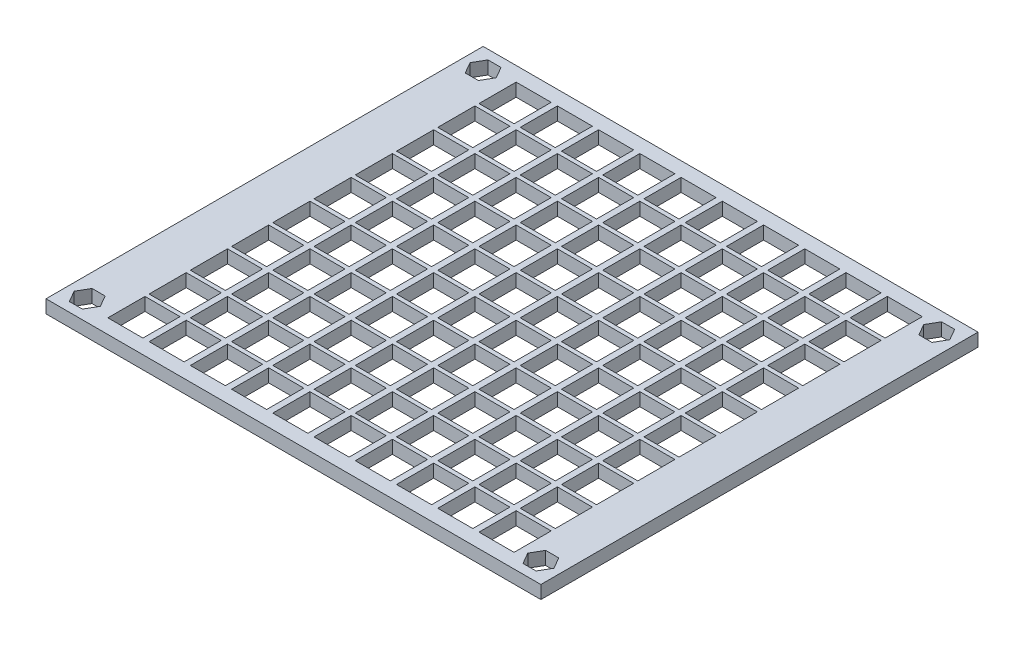
SolidWorks part; units mm, degrees
ref_plane "Front Plane" through (0, 0, 0) normal (0, 0, 1) x (1, 0, 0)
ref_plane "Top Plane" through (0, 0, 0) normal (0, 1, 0) x (1, 0, 0)
ref_plane "Right Plane" through (0, 0, 0) normal (1, 0, 0) x (0, 0, -1)
sketch "Sketch1" plane through (0, 0, 0) normal (0, 1, 0) x (1, 0, 0)
  line L0 (115, 101) -> (5, 101) construction
  line L1 (0, 0) -> (120, 0)
  line L2 (0, 0) -> (0, 106)
  line L3 (0, 106) -> (120, 106)
  line L4 (120, 0) -> (120, 106)
  line L6 (115, 101) -> (115, 5) construction
  line L8 (6.5877, 98.25) -> (8.1754, 101)
  line L9 (8.1754, 101) -> (6.5877, 103.75)
  line L10 (6.5877, 103.75) -> (3.4123, 103.75)
  line L11 (3.4123, 103.75) -> (1.8246, 101)
  line L12 (1.8246, 101) -> (3.4123, 98.25)
  line L13 (3.4123, 98.25) -> (6.5877, 98.25)
  line L14 (21.5, 12.5) -> (21.5, 3.5)
  line L15 (11.5, 12.5) -> (20, 12.5)
  line L16 (11.5, 12.5) -> (11.5, 3.5)
  line L17 (11.5, 3.5) -> (20, 3.5)
  line L18 (20, 12.5) -> (20, 3.5)
  line L19 (21.5, 12.5) -> (30, 12.5)
  line L20 (30, 12.5) -> (30, 3.5)
  line L21 (21.5, 3.5) -> (30, 3.5)
  line L22 (31.5, 12.5) -> (31.5, 3.5)
  line L23 (31.5, 12.5) -> (40, 12.5)
  line L24 (40, 12.5) -> (40, 3.5)
  line L25 (31.5, 3.5) -> (40, 3.5)
  line L26 (41.5, 12.5) -> (41.5, 3.5)
  line L27 (41.5, 12.5) -> (50, 12.5)
  line L28 (50, 12.5) -> (50, 3.5)
  line L29 (41.5, 3.5) -> (50, 3.5)
  line L30 (51.5, 12.5) -> (51.5, 3.5)
  line L31 (51.5, 12.5) -> (60, 12.5)
  line L32 (60, 12.5) -> (60, 3.5)
  line L33 (51.5, 3.5) -> (60, 3.5)
  line L34 (61.5, 12.5) -> (61.5, 3.5)
  line L35 (61.5, 12.5) -> (70, 12.5)
  line L36 (70, 12.5) -> (70, 3.5)
  line L37 (61.5, 3.5) -> (70, 3.5)
  line L38 (71.5, 12.5) -> (71.5, 3.5)
  line L39 (71.5, 12.5) -> (80, 12.5)
  line L40 (80, 12.5) -> (80, 3.5)
  line L41 (71.5, 3.5) -> (80, 3.5)
  line L42 (81.5, 12.5) -> (81.5, 3.5)
  line L43 (81.5, 12.5) -> (90, 12.5)
  line L44 (90, 12.5) -> (90, 3.5)
  line L45 (81.5, 3.5) -> (90, 3.5)
  line L46 (91.5, 12.5) -> (91.5, 3.5)
  line L47 (91.5, 12.5) -> (100, 12.5)
  line L48 (100, 12.5) -> (100, 3.5)
  line L49 (91.5, 3.5) -> (100, 3.5)
  line L50 (101.5, 12.5) -> (101.5, 3.5)
  line L51 (101.5, 12.5) -> (110, 12.5)
  line L52 (110, 12.5) -> (110, 3.5)
  line L53 (101.5, 3.5) -> (110, 3.5)
  line L54 (21.5, 22.5) -> (21.5, 13.5)
  line L55 (21.5, 22.5) -> (30, 22.5)
  line L56 (30, 22.5) -> (30, 13.5)
  line L57 (21.5, 13.5) -> (30, 13.5)
  line L58 (31.5, 22.5) -> (31.5, 13.5)
  line L59 (31.5, 22.5) -> (40, 22.5)
  line L60 (40, 22.5) -> (40, 13.5)
  line L61 (31.5, 13.5) -> (40, 13.5)
  line L62 (41.5, 22.5) -> (41.5, 13.5)
  line L63 (41.5, 22.5) -> (50, 22.5)
  line L64 (50, 22.5) -> (50, 13.5)
  line L65 (41.5, 13.5) -> (50, 13.5)
  line L66 (51.5, 22.5) -> (51.5, 13.5)
  line L67 (51.5, 22.5) -> (60, 22.5)
  line L68 (60, 22.5) -> (60, 13.5)
  line L69 (51.5, 13.5) -> (60, 13.5)
  line L70 (61.5, 22.5) -> (61.5, 13.5)
  line L71 (61.5, 22.5) -> (70, 22.5)
  line L72 (70, 22.5) -> (70, 13.5)
  line L73 (61.5, 13.5) -> (70, 13.5)
  line L74 (71.5, 22.5) -> (71.5, 13.5)
  line L75 (71.5, 22.5) -> (80, 22.5)
  line L76 (80, 22.5) -> (80, 13.5)
  line L77 (71.5, 13.5) -> (80, 13.5)
  line L78 (81.5, 22.5) -> (81.5, 13.5)
  line L79 (81.5, 22.5) -> (90, 22.5)
  line L80 (90, 22.5) -> (90, 13.5)
  line L81 (81.5, 13.5) -> (90, 13.5)
  line L82 (91.5, 22.5) -> (91.5, 13.5)
  line L83 (91.5, 22.5) -> (100, 22.5)
  line L84 (100, 22.5) -> (100, 13.5)
  line L85 (91.5, 13.5) -> (100, 13.5)
  line L86 (101.5, 22.5) -> (101.5, 13.5)
  line L87 (101.5, 22.5) -> (110, 22.5)
  line L88 (110, 22.5) -> (110, 13.5)
  line L89 (101.5, 13.5) -> (110, 13.5)
  line L90 (21.5, 32.5) -> (21.5, 23.5)
  line L91 (21.5, 32.5) -> (30, 32.5)
  line L92 (30, 32.5) -> (30, 23.5)
  line L93 (21.5, 23.5) -> (30, 23.5)
  line L94 (31.5, 32.5) -> (31.5, 23.5)
  line L95 (31.5, 32.5) -> (40, 32.5)
  line L96 (40, 32.5) -> (40, 23.5)
  line L97 (31.5, 23.5) -> (40, 23.5)
  line L98 (41.5, 32.5) -> (41.5, 23.5)
  line L99 (41.5, 32.5) -> (50, 32.5)
  line L100 (50, 32.5) -> (50, 23.5)
  line L101 (41.5, 23.5) -> (50, 23.5)
  line L102 (51.5, 32.5) -> (51.5, 23.5)
  line L103 (51.5, 32.5) -> (60, 32.5)
  line L104 (60, 32.5) -> (60, 23.5)
  line L105 (51.5, 23.5) -> (60, 23.5)
  line L106 (61.5, 32.5) -> (61.5, 23.5)
  line L107 (61.5, 32.5) -> (70, 32.5)
  line L108 (70, 32.5) -> (70, 23.5)
  line L109 (61.5, 23.5) -> (70, 23.5)
  line L110 (71.5, 32.5) -> (71.5, 23.5)
  line L111 (71.5, 32.5) -> (80, 32.5)
  line L112 (80, 32.5) -> (80, 23.5)
  line L113 (71.5, 23.5) -> (80, 23.5)
  line L114 (81.5, 32.5) -> (81.5, 23.5)
  line L115 (81.5, 32.5) -> (90, 32.5)
  line L116 (90, 32.5) -> (90, 23.5)
  line L117 (81.5, 23.5) -> (90, 23.5)
  line L118 (91.5, 32.5) -> (91.5, 23.5)
  line L119 (91.5, 32.5) -> (100, 32.5)
  line L120 (100, 32.5) -> (100, 23.5)
  line L121 (91.5, 23.5) -> (100, 23.5)
  line L122 (101.5, 32.5) -> (101.5, 23.5)
  line L123 (101.5, 32.5) -> (110, 32.5)
  line L124 (110, 32.5) -> (110, 23.5)
  line L125 (101.5, 23.5) -> (110, 23.5)
  line L126 (21.5, 42.5) -> (21.5, 33.5)
  line L127 (21.5, 42.5) -> (30, 42.5)
  line L128 (30, 42.5) -> (30, 33.5)
  line L129 (21.5, 33.5) -> (30, 33.5)
  line L130 (31.5, 42.5) -> (31.5, 33.5)
  line L131 (31.5, 42.5) -> (40, 42.5)
  line L132 (40, 42.5) -> (40, 33.5)
  line L133 (31.5, 33.5) -> (40, 33.5)
  line L134 (41.5, 42.5) -> (41.5, 33.5)
  line L135 (41.5, 42.5) -> (50, 42.5)
  line L136 (50, 42.5) -> (50, 33.5)
  line L137 (41.5, 33.5) -> (50, 33.5)
  line L138 (51.5, 42.5) -> (51.5, 33.5)
  line L139 (51.5, 42.5) -> (60, 42.5)
  line L140 (60, 42.5) -> (60, 33.5)
  line L141 (51.5, 33.5) -> (60, 33.5)
  line L142 (61.5, 42.5) -> (61.5, 33.5)
  line L143 (61.5, 42.5) -> (70, 42.5)
  line L144 (70, 42.5) -> (70, 33.5)
  line L145 (61.5, 33.5) -> (70, 33.5)
  line L146 (71.5, 42.5) -> (71.5, 33.5)
  line L147 (71.5, 42.5) -> (80, 42.5)
  line L148 (80, 42.5) -> (80, 33.5)
  line L149 (71.5, 33.5) -> (80, 33.5)
  line L150 (81.5, 42.5) -> (81.5, 33.5)
  line L151 (81.5, 42.5) -> (90, 42.5)
  line L152 (90, 42.5) -> (90, 33.5)
  line L153 (81.5, 33.5) -> (90, 33.5)
  line L154 (91.5, 42.5) -> (91.5, 33.5)
  line L155 (91.5, 42.5) -> (100, 42.5)
  line L156 (100, 42.5) -> (100, 33.5)
  line L157 (91.5, 33.5) -> (100, 33.5)
  line L158 (101.5, 42.5) -> (101.5, 33.5)
  line L159 (101.5, 42.5) -> (110, 42.5)
  line L160 (110, 42.5) -> (110, 33.5)
  line L161 (101.5, 33.5) -> (110, 33.5)
  line L162 (21.5, 52.5) -> (21.5, 43.5)
  line L163 (21.5, 52.5) -> (30, 52.5)
  line L164 (30, 52.5) -> (30, 43.5)
  line L165 (21.5, 43.5) -> (30, 43.5)
  line L166 (31.5, 52.5) -> (31.5, 43.5)
  line L167 (31.5, 52.5) -> (40, 52.5)
  line L168 (40, 52.5) -> (40, 43.5)
  line L169 (31.5, 43.5) -> (40, 43.5)
  line L170 (41.5, 52.5) -> (41.5, 43.5)
  line L171 (41.5, 52.5) -> (50, 52.5)
  line L172 (50, 52.5) -> (50, 43.5)
  line L173 (41.5, 43.5) -> (50, 43.5)
  line L174 (51.5, 52.5) -> (51.5, 43.5)
  line L175 (51.5, 52.5) -> (60, 52.5)
  line L176 (60, 52.5) -> (60, 43.5)
  line L177 (51.5, 43.5) -> (60, 43.5)
  line L178 (61.5, 52.5) -> (61.5, 43.5)
  line L179 (61.5, 52.5) -> (70, 52.5)
  line L180 (70, 52.5) -> (70, 43.5)
  line L181 (61.5, 43.5) -> (70, 43.5)
  line L182 (71.5, 52.5) -> (71.5, 43.5)
  line L183 (71.5, 52.5) -> (80, 52.5)
  line L184 (80, 52.5) -> (80, 43.5)
  line L185 (71.5, 43.5) -> (80, 43.5)
  line L186 (81.5, 52.5) -> (81.5, 43.5)
  line L187 (81.5, 52.5) -> (90, 52.5)
  line L188 (90, 52.5) -> (90, 43.5)
  line L189 (81.5, 43.5) -> (90, 43.5)
  line L190 (91.5, 52.5) -> (91.5, 43.5)
  line L191 (91.5, 52.5) -> (100, 52.5)
  line L192 (100, 52.5) -> (100, 43.5)
  line L193 (91.5, 43.5) -> (100, 43.5)
  line L194 (101.5, 52.5) -> (101.5, 43.5)
  line L195 (101.5, 52.5) -> (110, 52.5)
  line L196 (110, 52.5) -> (110, 43.5)
  line L197 (101.5, 43.5) -> (110, 43.5)
  line L198 (21.5, 62.5) -> (21.5, 53.5)
  line L199 (21.5, 62.5) -> (30, 62.5)
  line L200 (30, 62.5) -> (30, 53.5)
  line L201 (21.5, 53.5) -> (30, 53.5)
  line L202 (31.5, 62.5) -> (31.5, 53.5)
  line L203 (31.5, 62.5) -> (40, 62.5)
  line L204 (40, 62.5) -> (40, 53.5)
  line L205 (31.5, 53.5) -> (40, 53.5)
  line L206 (41.5, 62.5) -> (41.5, 53.5)
  line L207 (41.5, 62.5) -> (50, 62.5)
  line L208 (50, 62.5) -> (50, 53.5)
  line L209 (41.5, 53.5) -> (50, 53.5)
  line L210 (51.5, 62.5) -> (51.5, 53.5)
  line L211 (51.5, 62.5) -> (60, 62.5)
  line L212 (60, 62.5) -> (60, 53.5)
  line L213 (51.5, 53.5) -> (60, 53.5)
  line L214 (61.5, 62.5) -> (61.5, 53.5)
  line L215 (61.5, 62.5) -> (70, 62.5)
  line L216 (70, 62.5) -> (70, 53.5)
  line L217 (61.5, 53.5) -> (70, 53.5)
  line L218 (71.5, 62.5) -> (71.5, 53.5)
  line L219 (71.5, 62.5) -> (80, 62.5)
  line L220 (80, 62.5) -> (80, 53.5)
  line L221 (71.5, 53.5) -> (80, 53.5)
  line L222 (81.5, 62.5) -> (81.5, 53.5)
  line L223 (81.5, 62.5) -> (90, 62.5)
  line L224 (90, 62.5) -> (90, 53.5)
  line L225 (81.5, 53.5) -> (90, 53.5)
  line L226 (91.5, 62.5) -> (91.5, 53.5)
  line L227 (91.5, 62.5) -> (100, 62.5)
  line L228 (100, 62.5) -> (100, 53.5)
  line L229 (91.5, 53.5) -> (100, 53.5)
  line L230 (101.5, 62.5) -> (101.5, 53.5)
  line L231 (101.5, 62.5) -> (110, 62.5)
  line L232 (110, 62.5) -> (110, 53.5)
  line L233 (101.5, 53.5) -> (110, 53.5)
  line L234 (21.5, 72.5) -> (21.5, 63.5)
  line L235 (21.5, 72.5) -> (30, 72.5)
  line L236 (30, 72.5) -> (30, 63.5)
  line L237 (21.5, 63.5) -> (30, 63.5)
  line L238 (31.5, 72.5) -> (31.5, 63.5)
  line L239 (31.5, 72.5) -> (40, 72.5)
  line L240 (40, 72.5) -> (40, 63.5)
  line L241 (31.5, 63.5) -> (40, 63.5)
  line L242 (41.5, 72.5) -> (41.5, 63.5)
  line L243 (41.5, 72.5) -> (50, 72.5)
  line L244 (50, 72.5) -> (50, 63.5)
  line L245 (41.5, 63.5) -> (50, 63.5)
  line L246 (51.5, 72.5) -> (51.5, 63.5)
  line L247 (51.5, 72.5) -> (60, 72.5)
  line L248 (60, 72.5) -> (60, 63.5)
  line L249 (51.5, 63.5) -> (60, 63.5)
  line L250 (61.5, 72.5) -> (61.5, 63.5)
  line L251 (61.5, 72.5) -> (70, 72.5)
  line L252 (70, 72.5) -> (70, 63.5)
  line L253 (61.5, 63.5) -> (70, 63.5)
  line L254 (71.5, 72.5) -> (71.5, 63.5)
  line L255 (71.5, 72.5) -> (80, 72.5)
  line L256 (80, 72.5) -> (80, 63.5)
  line L257 (71.5, 63.5) -> (80, 63.5)
  line L258 (81.5, 72.5) -> (81.5, 63.5)
  line L259 (81.5, 72.5) -> (90, 72.5)
  line L260 (90, 72.5) -> (90, 63.5)
  line L261 (81.5, 63.5) -> (90, 63.5)
  line L262 (91.5, 72.5) -> (91.5, 63.5)
  line L263 (91.5, 72.5) -> (100, 72.5)
  line L264 (100, 72.5) -> (100, 63.5)
  line L265 (91.5, 63.5) -> (100, 63.5)
  line L266 (101.5, 72.5) -> (101.5, 63.5)
  line L267 (101.5, 72.5) -> (110, 72.5)
  line L268 (110, 72.5) -> (110, 63.5)
  line L269 (101.5, 63.5) -> (110, 63.5)
  line L270 (21.5, 82.5) -> (21.5, 73.5)
  line L271 (21.5, 82.5) -> (30, 82.5)
  line L272 (30, 82.5) -> (30, 73.5)
  line L273 (21.5, 73.5) -> (30, 73.5)
  line L274 (31.5, 82.5) -> (31.5, 73.5)
  line L275 (31.5, 82.5) -> (40, 82.5)
  line L276 (40, 82.5) -> (40, 73.5)
  line L277 (31.5, 73.5) -> (40, 73.5)
  line L278 (41.5, 82.5) -> (41.5, 73.5)
  line L279 (41.5, 82.5) -> (50, 82.5)
  line L280 (50, 82.5) -> (50, 73.5)
  line L281 (41.5, 73.5) -> (50, 73.5)
  line L282 (51.5, 82.5) -> (51.5, 73.5)
  line L283 (51.5, 82.5) -> (60, 82.5)
  line L284 (60, 82.5) -> (60, 73.5)
  line L285 (51.5, 73.5) -> (60, 73.5)
  line L286 (61.5, 82.5) -> (61.5, 73.5)
  line L287 (61.5, 82.5) -> (70, 82.5)
  line L288 (70, 82.5) -> (70, 73.5)
  line L289 (61.5, 73.5) -> (70, 73.5)
  line L290 (71.5, 82.5) -> (71.5, 73.5)
  line L291 (71.5, 82.5) -> (80, 82.5)
  line L292 (80, 82.5) -> (80, 73.5)
  line L293 (71.5, 73.5) -> (80, 73.5)
  line L294 (81.5, 82.5) -> (81.5, 73.5)
  line L295 (81.5, 82.5) -> (90, 82.5)
  line L296 (90, 82.5) -> (90, 73.5)
  line L297 (81.5, 73.5) -> (90, 73.5)
  line L298 (91.5, 82.5) -> (91.5, 73.5)
  line L299 (91.5, 82.5) -> (100, 82.5)
  line L300 (100, 82.5) -> (100, 73.5)
  line L301 (91.5, 73.5) -> (100, 73.5)
  line L302 (101.5, 82.5) -> (101.5, 73.5)
  line L303 (101.5, 82.5) -> (110, 82.5)
  line L304 (110, 82.5) -> (110, 73.5)
  line L305 (101.5, 73.5) -> (110, 73.5)
  line L306 (21.5, 92.5) -> (21.5, 83.5)
  line L307 (21.5, 92.5) -> (30, 92.5)
  line L308 (30, 92.5) -> (30, 83.5)
  line L309 (21.5, 83.5) -> (30, 83.5)
  line L310 (31.5, 92.5) -> (31.5, 83.5)
  line L311 (31.5, 92.5) -> (40, 92.5)
  line L312 (40, 92.5) -> (40, 83.5)
  line L313 (31.5, 83.5) -> (40, 83.5)
  line L314 (41.5, 92.5) -> (41.5, 83.5)
  line L315 (41.5, 92.5) -> (50, 92.5)
  line L316 (50, 92.5) -> (50, 83.5)
  line L317 (41.5, 83.5) -> (50, 83.5)
  line L318 (51.5, 92.5) -> (51.5, 83.5)
  line L319 (51.5, 92.5) -> (60, 92.5)
  line L320 (60, 92.5) -> (60, 83.5)
  line L321 (51.5, 83.5) -> (60, 83.5)
  line L322 (61.5, 92.5) -> (61.5, 83.5)
  line L323 (61.5, 92.5) -> (70, 92.5)
  line L324 (70, 92.5) -> (70, 83.5)
  line L325 (61.5, 83.5) -> (70, 83.5)
  line L326 (71.5, 92.5) -> (71.5, 83.5)
  line L327 (71.5, 92.5) -> (80, 92.5)
  line L328 (80, 92.5) -> (80, 83.5)
  line L329 (71.5, 83.5) -> (80, 83.5)
  line L330 (81.5, 92.5) -> (81.5, 83.5)
  line L331 (81.5, 92.5) -> (90, 92.5)
  line L332 (90, 92.5) -> (90, 83.5)
  line L333 (81.5, 83.5) -> (90, 83.5)
  line L334 (91.5, 92.5) -> (91.5, 83.5)
  line L335 (91.5, 92.5) -> (100, 92.5)
  line L336 (100, 92.5) -> (100, 83.5)
  line L337 (91.5, 83.5) -> (100, 83.5)
  line L338 (101.5, 92.5) -> (101.5, 83.5)
  line L339 (101.5, 92.5) -> (110, 92.5)
  line L340 (110, 92.5) -> (110, 83.5)
  line L341 (101.5, 83.5) -> (110, 83.5)
  line L342 (21.5, 102.5) -> (21.5, 93.5)
  line L343 (21.5, 102.5) -> (30, 102.5)
  line L344 (30, 102.5) -> (30, 93.5)
  line L345 (21.5, 93.5) -> (30, 93.5)
  line L346 (31.5, 102.5) -> (31.5, 93.5)
  line L347 (31.5, 102.5) -> (40, 102.5)
  line L348 (40, 102.5) -> (40, 93.5)
  line L349 (31.5, 93.5) -> (40, 93.5)
  line L350 (41.5, 102.5) -> (41.5, 93.5)
  line L351 (41.5, 102.5) -> (50, 102.5)
  line L352 (50, 102.5) -> (50, 93.5)
  line L353 (41.5, 93.5) -> (50, 93.5)
  line L354 (51.5, 102.5) -> (51.5, 93.5)
  line L355 (51.5, 102.5) -> (60, 102.5)
  line L356 (60, 102.5) -> (60, 93.5)
  line L357 (51.5, 93.5) -> (60, 93.5)
  line L358 (61.5, 102.5) -> (61.5, 93.5)
  line L359 (61.5, 102.5) -> (70, 102.5)
  line L360 (70, 102.5) -> (70, 93.5)
  line L361 (61.5, 93.5) -> (70, 93.5)
  line L362 (71.5, 102.5) -> (71.5, 93.5)
  line L363 (71.5, 102.5) -> (80, 102.5)
  line L364 (80, 102.5) -> (80, 93.5)
  line L365 (71.5, 93.5) -> (80, 93.5)
  line L366 (81.5, 102.5) -> (81.5, 93.5)
  line L367 (81.5, 102.5) -> (90, 102.5)
  line L368 (90, 102.5) -> (90, 93.5)
  line L369 (81.5, 93.5) -> (90, 93.5)
  line L370 (91.5, 102.5) -> (91.5, 93.5)
  line L371 (91.5, 102.5) -> (100, 102.5)
  line L372 (100, 102.5) -> (100, 93.5)
  line L373 (91.5, 93.5) -> (100, 93.5)
  line L374 (101.5, 102.5) -> (101.5, 93.5)
  line L375 (101.5, 102.5) -> (110, 102.5)
  line L376 (110, 102.5) -> (110, 93.5)
  line L377 (101.5, 93.5) -> (110, 93.5)
  line L378 (11.5, 22.5) -> (11.5, 13.5)
  line L379 (11.5, 22.5) -> (20, 22.5)
  line L380 (20, 22.5) -> (20, 13.5)
  line L381 (11.5, 13.5) -> (20, 13.5)
  line L382 (11.5, 32.5) -> (11.5, 23.5)
  line L383 (11.5, 32.5) -> (20, 32.5)
  line L384 (20, 32.5) -> (20, 23.5)
  line L385 (11.5, 23.5) -> (20, 23.5)
  line L386 (11.5, 42.5) -> (11.5, 33.5)
  line L387 (11.5, 42.5) -> (20, 42.5)
  line L388 (20, 42.5) -> (20, 33.5)
  line L389 (11.5, 33.5) -> (20, 33.5)
  line L390 (11.5, 52.5) -> (11.5, 43.5)
  line L391 (11.5, 52.5) -> (20, 52.5)
  line L392 (20, 52.5) -> (20, 43.5)
  line L393 (11.5, 43.5) -> (20, 43.5)
  line L394 (11.5, 62.5) -> (11.5, 53.5)
  line L395 (11.5, 62.5) -> (20, 62.5)
  line L396 (20, 62.5) -> (20, 53.5)
  line L397 (11.5, 53.5) -> (20, 53.5)
  line L398 (11.5, 72.5) -> (11.5, 63.5)
  line L399 (11.5, 72.5) -> (20, 72.5)
  line L400 (20, 72.5) -> (20, 63.5)
  line L401 (11.5, 63.5) -> (20, 63.5)
  line L402 (11.5, 82.5) -> (11.5, 73.5)
  line L403 (11.5, 82.5) -> (20, 82.5)
  line L404 (20, 82.5) -> (20, 73.5)
  line L405 (11.5, 73.5) -> (20, 73.5)
  line L406 (11.5, 92.5) -> (11.5, 83.5)
  line L407 (11.5, 92.5) -> (20, 92.5)
  line L408 (20, 92.5) -> (20, 83.5)
  line L409 (11.5, 83.5) -> (20, 83.5)
  line L410 (11.5, 102.5) -> (11.5, 93.5)
  line L411 (11.5, 102.5) -> (20, 102.5)
  line L412 (20, 102.5) -> (20, 93.5)
  line L413 (11.5, 93.5) -> (20, 93.5)
  line L415 (113.4123, 103.75) -> (111.8246, 101)
  line L416 (111.8246, 101) -> (113.4123, 98.25)
  line L417 (113.4123, 98.25) -> (116.5877, 98.25)
  line L418 (116.5877, 98.25) -> (118.1754, 101)
  line L419 (118.1754, 101) -> (116.5877, 103.75)
  line L420 (116.5877, 103.75) -> (113.4123, 103.75)
  line L421 (113.4123, 7.75) -> (111.8246, 5)
  line L422 (111.8246, 5) -> (113.4123, 2.25)
  line L423 (113.4123, 2.25) -> (116.5877, 2.25)
  line L424 (116.5877, 2.25) -> (118.1754, 5)
  line L425 (118.1754, 5) -> (116.5877, 7.75)
  line L426 (116.5877, 7.75) -> (113.4123, 7.75)
  line L427 (1.8246, 5) -> (3.4123, 2.25)
  line L428 (3.4123, 2.25) -> (6.5877, 2.25)
  line L429 (6.5877, 2.25) -> (8.1754, 5)
  line L430 (8.1754, 5) -> (6.5877, 7.75)
  line L431 (6.5877, 7.75) -> (3.4123, 7.75)
  line L432 (3.4123, 7.75) -> (1.8246, 5)
  circle A28 centre (5, 5) radius 1.7
  circle A29 centre (5, 101) radius 1.7
  circle A30 centre (115, 101) radius 1.7
  circle A31 centre (115, 5) radius 1.7
  circle A129 centre (5, 101) radius 2.75 construction
  circle A130 centre (115, 101) radius 2.75 construction
  circle A131 centre (115, 5) radius 2.75 construction
  circle A132 centre (5, 5) radius 2.75 construction
  point P7 (115, 53)
  point P9 (60, 101)
  point P10 (60, 106)
  point P20 (120, 53)
  point P25 (0, 0)
  point P31 (0, 0)
  point P441 (0, 0)
  dimension "D5" = 110
  dimension "D6" = 96
  dimension "D3" = 9
  dimension "D8" = 3.4
  dimension "D1" = 120
  dimension "D2" = 106
  dimension "D4" = 8.5
  dimension "D7" = 10
  dimension "D10" = 6.5
  dimension "D11" = 1.5
  dimension "D12" = 5.5
  dimension "D9" = 10
extrude "Boss-Extrude1" add sketch "Sketch1" along normal blind 3.175 contours L1 L4 L3 L2 region at (58.8445, 0, -53)
equation "\"o\"= 10mm"
equation "\"P\"= 10"
